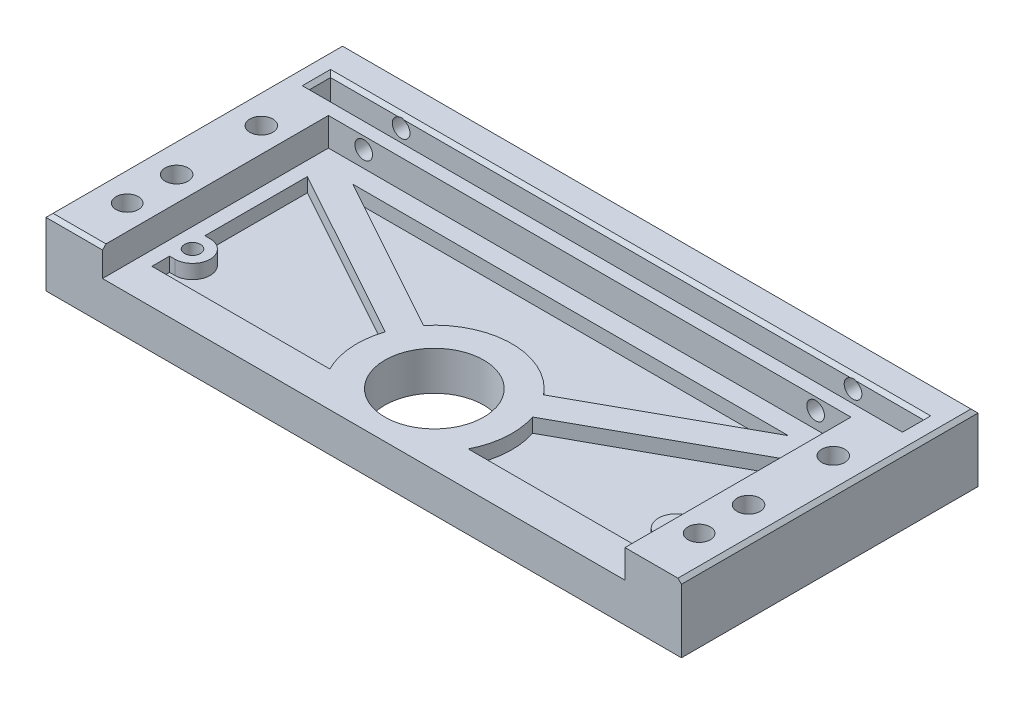
SolidWorks part; units mm, degrees
ref_plane "Front Plane" through (0, 0, 0) normal (0, 0, 1) x (1, 0, 0)
ref_plane "Top Plane" through (0, 0, 0) normal (0, 1, 0) x (1, 0, 0)
ref_plane "Right Plane" through (0, 0, 0) normal (1, 0, 0) x (0, 0, -1)
sketch "Sketch1" plane through (0, 0, 0) normal (0, 0, 1) x (1, 0, 0)
  line L1 (0, 0) -> (90, 0)
  line L2 (0, 0) -> (0, 9.525)
  line L3 (0, 9.525) -> (90, 9.525)
  line L4 (90, 0) -> (90, 9.525)
  circle A0 centre (30, 4.7625) radius 2
  circle A1 centre (60, 4.7625) radius 2
  point P7 (0, 4.7625)
  point P11 (45, 0)
  dimension "D5" = 4
  dimension "D1" = 90
  dimension "D2" = 9.525
  dimension "D3" = 15
  dimension "D4" = 15
extrude "Boss-Extrude1" add sketch "Sketch1" along normal blind 45 contours A1 | A0 | L1 L4 L3 L2 A1 A0
sketch "Sketch2" plane through (0, 9.525, 0) normal (0, 1, 0) x (1, 0, 0)
  line L0 (0, 0) -> (90, 0) construction
  circle A0 centre (45, -35) radius 7
  point P4 (45, 0)
  dimension "D2" = 14
  dimension "D1" = 35
extrude "Cut-Extrude2" cut sketch "Sketch2" against normal blind 10
sketch "Sketch3" plane through (0, 9.525, 0) normal (0, 1, 0) x (1, 0, 0)
  line L0 (90, -45) -> (90, 0) construction
  line L1 (0, -45) -> (0, 0) construction
  circle A0 centre (85.5, -31) radius 1.632
  circle A1 centre (4.5, -31) radius 1.632
  circle A2 centre (45, -35) radius 7 construction
  circle A3 centre (45, -35) radius 7
  circle A4 centre (85.5, -19) radius 1.632
  circle A5 centre (4.5, -19) radius 1.632
  circle A6 centre (79.25, -35) radius 1.1303
  circle A7 centre (10.75, -35) radius 1.1303
  dimension "D1" = 3.2639
  dimension "D8" = 34.25
  dimension "D9" = 2.2606
  dimension "D2" = 4.5
  dimension "D3" = 4.5
  dimension "D5" = 12
  dimension "D6" = 4
  dimension "D7" = 34.25
  dimension "D4" = 2
extrude "Cut-Extrude3" cut sketch "Sketch3" against normal blind 10
sketch "Sketch4" plane through (0, 9.525, 0) normal (0, 1, 0) x (1, 0, 0)
  line L1 (87, -7.7) -> (3, -7.7)
  line L2 (87, -7.7) -> (87, -10.7)
  line L3 (87, -10.7) -> (3, -10.7)
  line L4 (3, -7.7) -> (3, -10.7)
  line L6 (90, -45) -> (90, 0) construction
  line L7 (0, -45) -> (0, 0) construction
  circle A0 centre (45, -35) radius 7 construction
  dimension "D1" = 24.3
  dimension "D2" = 3
  dimension "D3" = 3
  dimension "D4" = 3
extrude "Cut-Extrude4" cut sketch "Sketch4" against normal blind 6
sketch "Sketch6" plane through (0, 9.525, 0) normal (0, 1, 0) x (1, 0, 0)
  line L0 (10.75, -37.5) -> (10, -37.5)
  line L1 (10.75, -32.5) -> (10, -32.5)
  line L2 (79.25, -37.5) -> (80, -37.5)
  line L3 (79.25, -32.5) -> (80, -32.5)
  line L4 (80, -32.5) -> (80, -15.7)
  line L5 (54.798, -40) -> (80, -40)
  line L6 (80, -40) -> (80, -37.5)
  line L7 (80, -15.7) -> (10, -15.7)
  line L8 (10, -15.7) -> (10, -32.5)
  line L9 (90, -45) -> (90, 0)
  line L10 (90, 0) -> (0, 0)
  line L11 (0, 0) -> (0, -45)
  line L12 (0, -45) -> (90, -45)
  line L13 (90, -45) -> (90, 0)
  line L15 (0, 0) -> (0, -45)
  line L16 (0, -45) -> (90, -45)
  line L17 (10, -40) -> (35.202, -40)
  line L18 (3, -10.7) -> (87, -10.7) construction
  line L19 (80, -15.7) -> (45, -35) construction
  line L20 (45, -35) -> (10, -15.7) construction
  line L21 (80, -17.9839) -> (55.4378, -31.5282)
  line L22 (75.8582, -15.7) -> (53.5062, -28.0255)
  line L23 (36.4938, -28.0255) -> (14.1418, -15.7)
  line L24 (34.5622, -31.5282) -> (10, -17.9839)
  line L25 (10, -37.5) -> (10, -40)
  line L29 (90, 0) -> (0, 0)
  arc A0 (10.75, -37.5) -> (10.75, -32.5) centre (10.75, -35) ccw
  circle A1 centre (45, -35) radius 11
  arc A2 (79.25, -32.5) -> (79.25, -37.5) centre (79.25, -35) ccw
  dimension "D2" = 22
  dimension "D11" = 5
  dimension "D12" = 5
  dimension "D3" = 5
  dimension "D4" = 10
  dimension "D5" = 5
  dimension "D6" = 10
  dimension "D7" = 2
  dimension "D8" = 4
  dimension "D9" = 2
  dimension "D10" = 4
  dimension "D1" = 0
extrude "Cut-Extrude6" cut sketch "Sketch6" against normal blind 6 and the other way through all contours A1 L5 L6 L21 | A1 L22 L7 L23 | A1 L24 L8 L17
sketch "Sketch7" plane through (0, 9.525, 0) normal (0, 1, 0) x (1, 0, 0)
  line L0 (0, -45) -> (0, 0) construction
  line L1 (90, 0) -> (0, 0)
  line L2 (90, 0) -> (90, -3)
  line L3 (90, -3) -> (0, -3)
  line L4 (0, 0) -> (0, -3)
  dimension "D1" = 3
extrude "Cut-Extrude7" cut sketch "Sketch7" against normal blind 10
sketch "Sketch9" plane through (0, 9.525, 0) normal (0, 1, 0) x (1, 0, 0)
  line L0 (0, -45) -> (90, -45) construction
  line L1 (82, -45) -> (8, -45)
  line L2 (82, -45) -> (82, -13)
  line L3 (82, -13) -> (8, -13)
  line L4 (8, -45) -> (8, -13)
  line L5 (90, -45) -> (90, -3) construction
  line L6 (0, -45) -> (0, -3) construction
  line L7 (0, -3) -> (90, -3) construction
  dimension "D1" = 8
  dimension "D2" = 8
  dimension "D3" = 10
extrude "Cut-Extrude8" cut sketch "Sketch9" against normal blind 4
sketch "Sketch10" plane through (0, 0, 13) normal (0, 0, 1) x (1, 0, 0)
  line L0 (82, 5.525) -> (82, 9.525) construction
  line L1 (8, 5.525) -> (8, 9.525) construction
  line L2 (82, 9.525) -> (8, 9.525) construction
  circle A0 centre (77, 7.825) radius 1.25
  circle A1 centre (13, 7.825) radius 1.25
  dimension "D1" = 2.5
  dimension "D2" = 5
  dimension "D3" = 5
  dimension "D4" = 1.7
extrude "Cut-Extrude9" cut sketch "Sketch10" against normal up to surface (10 mm away) up to face at (45, 4.7625, 3)
chamfer "Chamfer2" distance 0.5 angle 45 7 edges at (45, 9.525, 3) (87, 9.525, 9.2) (45, 9.525, 7.7) (3, 9.525, 9.2) (45, 9.525, 10.7) (0, 9.525, 24) (90, 9.525, 24)
sketch "Sketch11" plane through (0, 9.525, 0) normal (0, 1, 0) x (1, 0, 0)
  circle A0 centre (85.5, -38) radius 1.5875
  circle A1 centre (85.5, -31) radius 1.632 construction
  circle A2 centre (85.5, -31) radius 1.632
  circle A3 centre (4.5, -38) radius 1.5875
  circle A4 centre (4.5, -31) radius 1.632 construction
  circle A5 centre (4.5, -31) radius 1.632
  dimension "D2" = 3.175
  dimension "D1" = 7
extrude "Cut-Extrude10" cut sketch "Sketch11" against normal blind 4 contours A0 | A3
